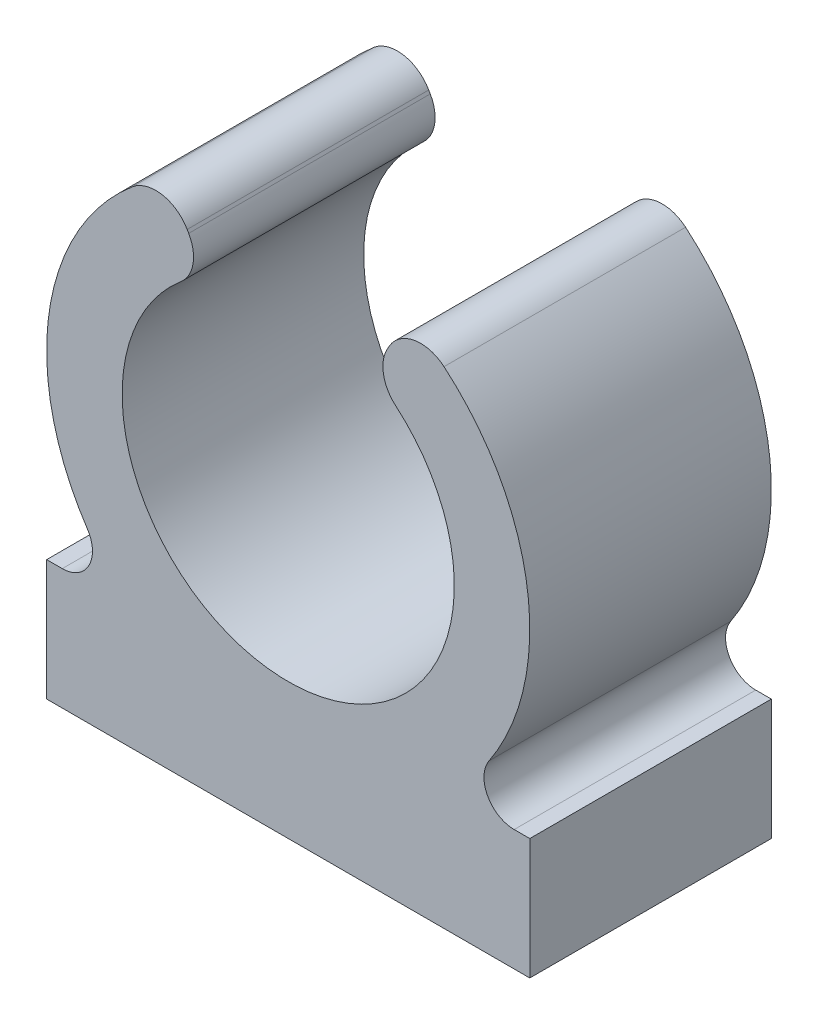
SolidWorks part; units mm, degrees
ref_plane "前视基准面" through (0, 0, 0) normal (0, 0, 1) x (1, 0, 0)
ref_plane "上视基准面" through (0, 0, 0) normal (0, 1, 0) x (1, 0, 0)
ref_plane "右视基准面" through (0, 0, 0) normal (1, 0, 0) x (0, 0, -1)
other "Configuration Table"
sketch "草图1" plane through (0, 0, 0) normal (0, 1, 0) x (1, 0, 0)
  line L1 (0, 0) -> (8, 0)
  line L2 (0, 0) -> (0, 4)
  line L3 (0, 4) -> (8, 4)
  line L4 (8, 0) -> (8, 4)
  dimension "D1" = 8
  dimension "D2" = 4
extrude "凸台-拉伸1" add sketch "草图1" along normal blind 1
sketch "草图2" plane through (0, 0, 0) normal (0, 0, 1) x (1, 0, 0)
  line L0 (0, 1) -> (8, 1) construction
  line L1 (8, 1) -> (0, 1)
  line L2 (8, 1) -> (8, 0) construction
  line L3 (2.3521, 7.8543) -> (2.3267, 7.8983)
  line L5 (4, 1) -> (4, 12) construction
  line L6 (5.6479, 7.8543) -> (5.6733, 7.8983)
  arc A0 (1.4201, 8.0568) -> (6.5799, 8.0568) centre (4, 5) ccw
  arc A1 (2.2207, 7.0968) -> (5.7793, 7.0968) centre (4, 5) ccw
  arc A2 (5.6733, 7.8983) -> (6.5799, 8.0568) centre (6.1929, 7.5983) cw
  arc A3 (5.6479, 7.8543) -> (5.7793, 7.0968) centre (6.1675, 7.5543) ccw
  arc A4 (2.2207, 7.0968) -> (2.3521, 7.8543) centre (1.8325, 7.5543) ccw
  arc A5 (2.3267, 7.8983) -> (1.4201, 8.0568) centre (1.8071, 7.5983) ccw
  point P4 (4, 1)
  point P17 (0, 0)
  point P18 (0, 0)
  point P20 (6, 8.4641)
  point P23 (5.375, 7.3816)
  point P26 (2.625, 7.3816)
  point P29 (2, 8.4641)
  point P30 (5, 2)
  dimension "D1" = 1.25
  dimension "D3" = 0.6
  dimension "D2" = 30
extrude "凸台-拉伸2" add sketch "草图2" against normal up to surface (4 mm away) separate body contours L5 A0 A2 L6 A3 A1 | A0 L5 A1 A4 L3 A5 region at (2.3425, 7.4658, 0) region at (6.6588, 4.0239, 0) up to face at (4, 0.5, -4)
extrude "凸台-拉伸3" add sketch "草图1<2>" along normal blind 2
sketch "草图1<2>" plane through (0, 0, 0) normal (0, 1, 0) x (1, 0, 0) same geometry as "草图1"
fillet "圆角1" radius 0.5 2 edges at (1.3542, 2, -2) (6.6458, 2, -2)
